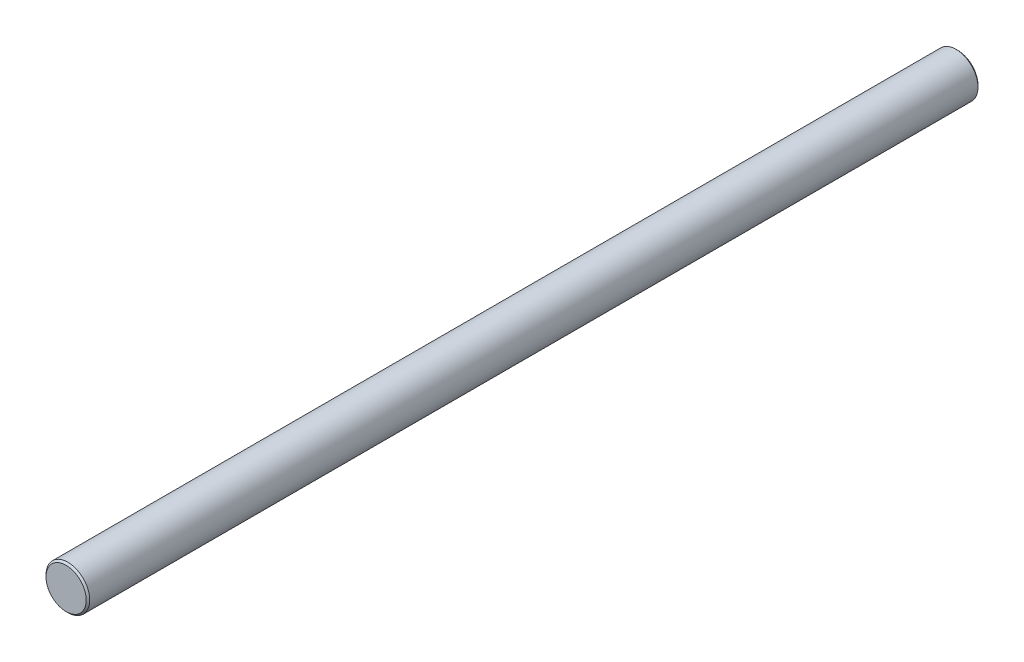
SolidWorks part; units mm, degrees
material "AISI 304"
ref_plane "Спереди" through (0, 0, 0) normal (0, 0, 1) x (1, 0, 0)
ref_plane "Сверху" through (0, 0, 0) normal (0, 1, 0) x (1, 0, 0)
ref_plane "Справа" through (0, 0, 0) normal (1, 0, 0) x (0, 0, -1)
ref_axis "ОсьX" through (-88.99, 0, 0) along (1, 0, 0)
ref_axis "ОсьZ" through (0, 55, 0) along (0, -1, 0)
ref_axis "ОсьY" through (0, 0, -88.99) along (0, 0, 1)
sketch "Эскиз1" plane through (0, 0, 0) normal (0, 0, 1) x (1, 0, 0)
  circle A0 centre (0, 0) radius 12.5
  dimension "D1" = 25
extrude "Бобышка-Вытянуть1" add sketch "Эскиз1" along normal mid plane 510
chamfer "Фаска1" distance 1 angle 45 2 edges at (12.5, 0, -255) (12.5, 0, 255)
